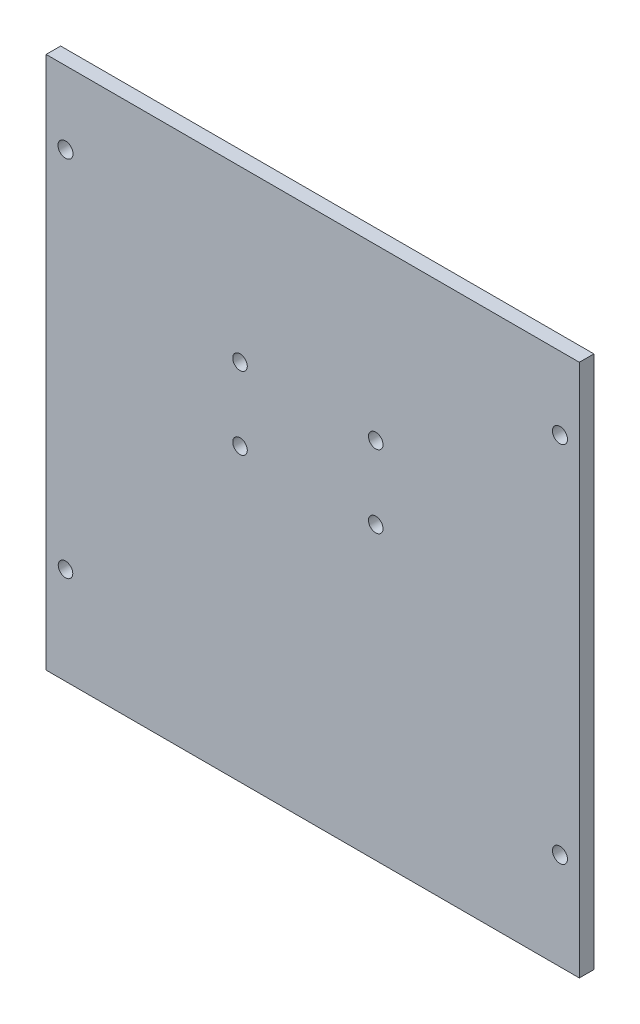
SolidWorks part; units mm, degrees
ref_plane "前视基准面" through (0, 0, 0) normal (0, 0, 1) x (1, 0, 0)
ref_plane "上视基准面" through (0, 0, 0) normal (0, 1, 0) x (1, 0, 0)
ref_plane "右视基准面" through (0, 0, 0) normal (1, 0, 0) x (0, 0, -1)
other "Configuration Table"
sketch "草图1" plane through (0, 0, 0) normal (0, 0, 1) x (1, 0, 0)
  line L1 (55, -55) -> (-55, -55)
  line L2 (55, -55) -> (55, 55)
  line L3 (55, 55) -> (-55, 55)
  line L4 (-55, -55) -> (-55, 55)
  line L5 (55, -55) -> (-55, 55) construction
  line L6 (55, 55) -> (-55, -55) construction
  point P0 (0, 0)
  dimension "D1" = 110
  dimension "D2" = 110
extrude "凸台-拉伸1" add sketch "草图1" along normal blind 3
sketch "草图2" plane through (0, 0, 0) normal (0, 0, -1) x (-1, 0, 0)
  circle A0 centre (-13, 5.02) radius 1.5
  circle A1 centre (-13, 20.02) radius 1.5
  circle A2 centre (15, 5.02) radius 1.5
  circle A3 centre (15, 20.02) radius 1.5
extrude "切除-拉伸1" cut sketch "草图2" against normal blind 10
sketch "草图3" plane through (0, 0, 0) normal (0, 0, -1) x (-1, 0, 0)
  circle A0 centre (-51, -35) radius 1.55
  circle A1 centre (-51, 40) radius 1.55
  circle A2 centre (51, -35) radius 1.5
  circle A3 centre (51, 40) radius 1.55
extrude "切除-拉伸2" cut sketch "草图3" against normal blind 10
